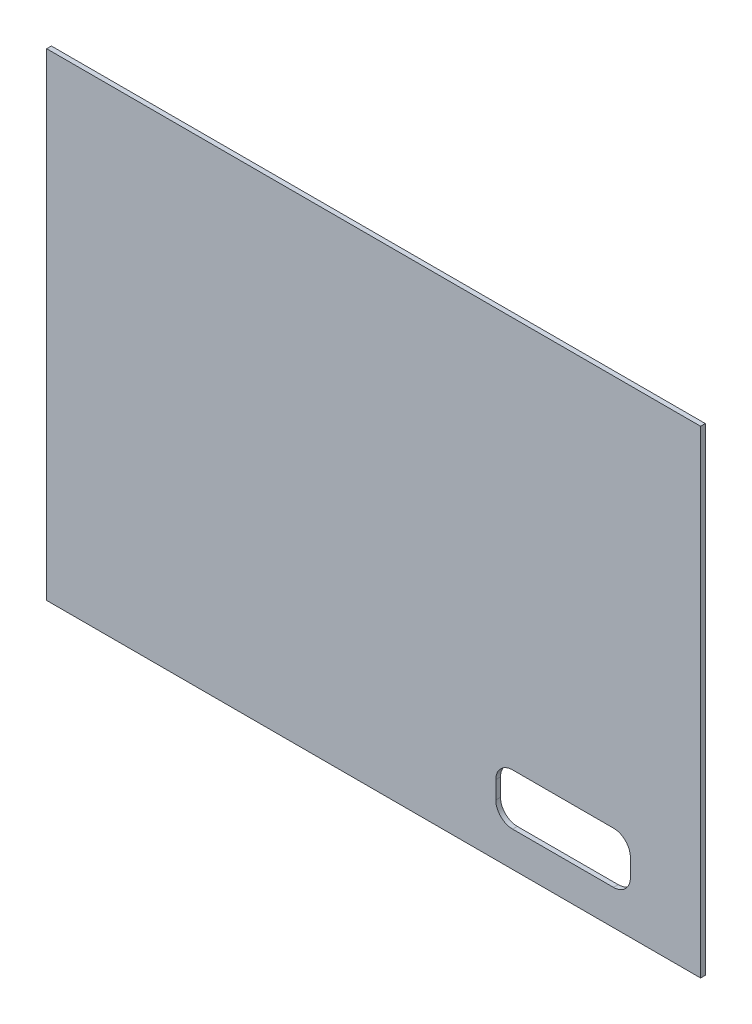
SolidWorks part; units mm, degrees
ref_plane "Front Plane" through (0, 0, 0) normal (0, 0, 1) x (1, 0, 0)
ref_plane "Top Plane" through (0, 0, 0) normal (0, 1, 0) x (1, 0, 0)
ref_plane "Right Plane" through (0, 0, 0) normal (1, 0, 0) x (0, 0, -1)
sketch "Sketch1" plane through (0, 0, 0) normal (0, 0, 1) x (1, 0, 0)
  line L0 (25.5163, 88.5062) -> (25.5163, -23.5303) construction
  line L1 (0, 0) -> (97.1664, 0)
  line L2 (0, 0) -> (0, 71)
  line L3 (0, 71) -> (97.1664, 71)
  line L4 (97.1664, 0) -> (97.1664, 71)
  line L5 (15.5163, 88.5062) -> (15.5163, -23.5303) construction
  line L6 (10.5163, 65) -> (20.5163, 65)
  line L7 (10.5163, 65) -> (15.5163, 53)
  line L8 (15.5163, 53) -> (20.5163, 65)
  line L9 (25.5163, 65) -> (25.5163, 54)
  line L10 (25.5163, 54) -> (18.2663, 36.6)
  line L11 (18.2663, 36.6) -> (18.2663, 47.6)
  line L12 (18.2663, 47.6) -> (25.5163, 65)
  line L13 (5.5163, 65) -> (12.7663, 47.6)
  line L14 (12.7663, 47.6) -> (12.7663, 36.6)
  line L15 (12.7663, 36.6) -> (5.5163, 54)
  line L16 (5.5163, 54) -> (5.5163, 65)
  line L17 (71.6501, 88.5062) -> (71.6501, -23.5303) construction
  line L18 (84.4001, 47.6) -> (91.6501, 65)
  line L19 (81.6501, 53) -> (86.6501, 65)
  line L20 (76.6501, 65) -> (86.6501, 65)
  line L21 (91.6501, 54) -> (84.4001, 36.6)
  line L22 (78.9001, 36.6) -> (71.6501, 54)
  line L23 (76.6501, 65) -> (81.6501, 53)
  line L24 (71.6501, 65) -> (78.9001, 47.6)
  line L25 (91.6501, 65) -> (91.6501, 54)
  line L26 (84.4001, 36.6) -> (84.4001, 47.6)
  line L27 (78.9001, 47.6) -> (78.9001, 36.6)
  line L28 (71.6501, 54) -> (71.6501, 65)
  line L29 (66.7319, 90.2077) -> (66.7319, -23.5303) construction
  line L30 (18.5163, 47.55) -> (25.2663, 63.75)
  line L31 (66.7319, 5.1907) -> (86.7319, 5.1907)
  line L32 (66.7319, 5.1907) -> (66.7319, 12.8107)
  line L33 (66.7319, 12.8107) -> (86.7319, 12.8107)
  line L34 (86.7319, 5.1907) -> (86.7319, 12.8107)
  line L35 (25.2663, 63.75) -> (25.2663, 54.05)
  line L36 (25.2663, 54.05) -> (18.5163, 37.85)
  line L37 (18.5163, 37.85) -> (18.5163, 47.55)
  line L38 (15.5163, 53.65) -> (20.1413, 64.75)
  line L39 (10.8913, 64.75) -> (20.1413, 64.75)
  line L40 (10.8913, 64.75) -> (15.5163, 53.65)
  line L41 (5.7663, 54.05) -> (5.7663, 63.75)
  line L42 (5.7663, 63.75) -> (12.5163, 47.55)
  line L43 (12.5163, 47.55) -> (12.5163, 37.85)
  line L44 (12.5163, 37.85) -> (5.7663, 54.05)
  line L45 (78.6501, 37.85) -> (71.9001, 54.05)
  line L46 (71.9001, 54.05) -> (71.9001, 63.75)
  line L47 (71.9001, 63.75) -> (78.6501, 47.55)
  line L48 (78.6501, 47.55) -> (78.6501, 37.85)
  line L49 (81.6501, 53.65) -> (86.2751, 64.75)
  line L50 (77.0251, 64.75) -> (86.2751, 64.75)
  line L51 (77.0251, 64.75) -> (81.6501, 53.65)
  line L52 (84.6501, 47.55) -> (91.4001, 63.75)
  line L53 (91.4001, 63.75) -> (91.4001, 54.05)
  line L54 (91.4001, 54.05) -> (84.6501, 37.85)
  line L55 (84.6501, 37.85) -> (84.6501, 47.55)
  point P12 (15.5163, 65)
  point P26 (81.644, 65)
  dimension "D1" = 97.1664
  dimension "D2" = 71
  dimension "D3" = 25.5163
  dimension "D4" = 10
  dimension "D5" = 10
  dimension "D6" = 12
  dimension "D7" = 11
  dimension "D8" = 28.4
  dimension "D9" = 28.4
  dimension "D10" = 5
  dimension "D11" = 2.75
  dimension "D12" = 6
  dimension "D13" = 25.5163
  dimension "D14" = 0
  dimension "D15" = 30.4345
  dimension "D16" = 5.1907
  dimension "D17" = 7.62
  dimension "D18" = 20
  dimension "D19" = 0.25
extrude "Boss-Extrude2" add sketch "Sketch1" along normal blind 0.7 contours L2 L1 L4 L3 | L32 L31 L34 L33
extrude "Boss-Extrude3" add sketch "Sketch1<4>" against normal blind 5 contours L37 L36 L35 L30 | L39 L40 L38 | L44 L43 L42 L41 | L50 L51 L49 | L48 L47 L46 L45 | L55 L54 L53 L52 region at (21.8913, 50.8, 0) region at (15.5163, 61.05, 0) region at (9.1413, 50.8, 0) region at (75.2751, 50.8, 0) region at (81.6501, 61.05, 0) region at (88.0251, 50.8, 0)
sketch "Sketch1<4>" plane through (0, 0, 0) normal (0, 0, 1) x (1, 0, 0) same geometry as "Sketch1"
fillet "Fillet1" radius 2.5 4 edges at (66.7319, 5.1907, 0.35) (66.7319, 12.8107, 0.35) (86.7319, 12.8107, 0.35) (86.7319, 5.1907, 0.35)
